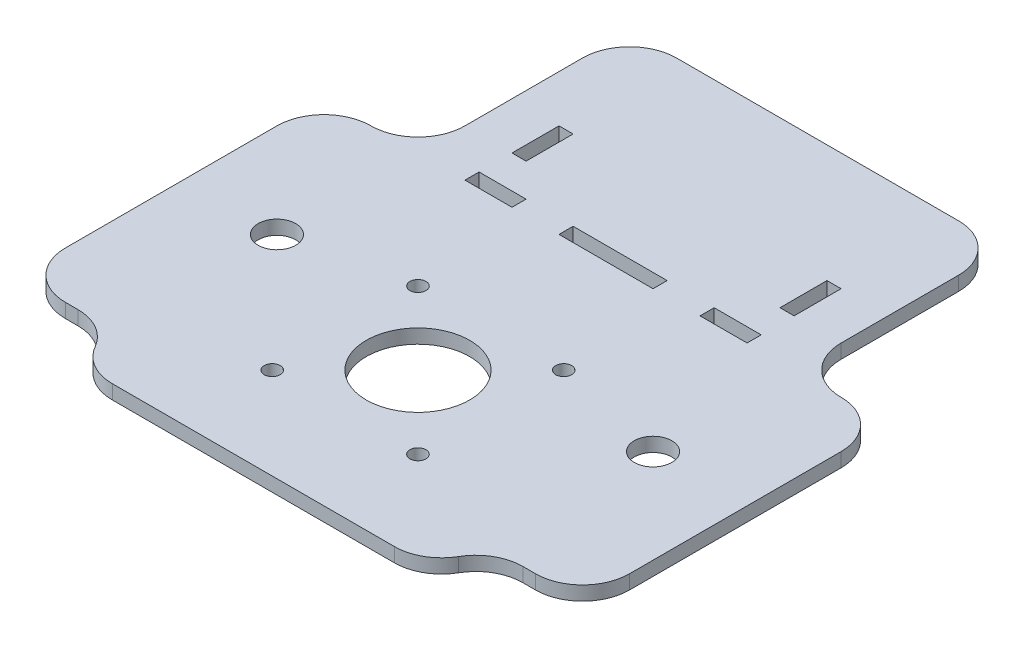
SolidWorks part; units mm, degrees
ref_plane "Front Plane" through (0, 0, 0) normal (0, 0, 1) x (1, 0, 0)
ref_plane "Top Plane" through (0, 0, 0) normal (0, 1, 0) x (1, 0, 0)
ref_plane "Right Plane" through (0, 0, 0) normal (1, 0, 0) x (0, 0, -1)
sketch "Sketch1" plane through (0, 0, 0) normal (0, 1, 0) x (1, 0, 0)
  line L1 (30, -45) -> (-30, -45)
  line L2 (30, -45) -> (30, 45)
  line L3 (30, 45) -> (-30, 45)
  line L4 (-30, -45) -> (-30, 45)
  line L5 (30, -45) -> (-30, 45) construction
  line L6 (30, 45) -> (-30, -45) construction
  point P0 (0, 0)
extrude "Boss-Extrude1" add sketch "Sketch1" along normal blind 3
sketch "Sketch2" plane through (0, 3, 0) normal (0, 1, 0) x (1, 0, 0)
  line L0 (30, 15) -> (20, 15)
  line L1 (30, 18) -> (20, 18)
  line L4 (-30, 45) -> (-30, -45)
  line L5 (-30, -45) -> (30, -45)
  line L6 (30, -45) -> (30, 45)
  line L7 (30, 45) -> (-30, 45)
  line L8 (-30, 35) -> (-30, 25)
  line L10 (30, 15) -> (30, 18)
  line L14 (-20, 18) -> (-20, 15)
  line L15 (-10, 18) -> (-10, 15)
  line L20 (-27, 35) -> (-27, 25)
  line L21 (-27, 25) -> (-30, 25)
  line L22 (27, 25) -> (27, 35)
  line L24 (10, 18) -> (10, 15)
  line L25 (20, 18) -> (20, 15)
  line L26 (10, 18) -> (-10, 18)
  line L27 (30, 18) -> (-30, 18) construction
  line L28 (10, 15) -> (-10, 15)
  line L29 (30, 15) -> (-30, 15) construction
  line L30 (-20, 18) -> (-30, 18)
  line L31 (-20, 15) -> (-30, 15)
  line L32 (30, 25) -> (27, 25)
  line L33 (-27, 35) -> (-30, 35)
  line L34 (30, 35) -> (27, 35)
  line L35 (-30, 18) -> (-30, 15)
  line L36 (30, 25) -> (30, 35)
  dimension "D1" = 0
  dimension "D3" = 3
extrude "Cut-Extrude2" cut sketch "Sketch2" against normal blind 3
sketch "Sketch3" plane through (0, 3, 0) normal (0, 1, 0) x (1, 0, 0)
  line L1 (40, -60) -> (-40, -60)
  line L2 (40, -60) -> (40, 60)
  line L3 (40, 60) -> (-40, 60)
  line L4 (-40, -60) -> (-40, 60)
  line L5 (40, -60) -> (-40, 60) construction
  line L6 (40, 60) -> (-40, -60) construction
  line L26 (-30, 18) -> (-20, 18)
  line L27 (-20, 18) -> (-20, 15)
  line L28 (-20, 15) -> (-30, 15)
  line L29 (-30, 15) -> (-30, -45)
  line L30 (-30, -45) -> (30, -45)
  line L31 (30, -45) -> (30, 15)
  line L32 (30, 15) -> (20, 15)
  line L33 (20, 15) -> (20, 18)
  line L34 (20, 18) -> (30, 18)
  line L35 (30, 18) -> (30, 25)
  line L36 (30, 25) -> (27, 25)
  line L37 (27, 25) -> (27, 35)
  line L38 (27, 35) -> (30, 35)
  line L39 (30, 35) -> (30, 45)
  line L40 (30, 45) -> (-30, 45)
  line L41 (-30, 45) -> (-30, 35)
  line L42 (-30, 35) -> (-27, 35)
  line L43 (-27, 35) -> (-27, 25)
  line L44 (-27, 25) -> (-30, 25)
  line L45 (-30, 25) -> (-30, 18)
  line L49 (-30, 18) -> (-30, -45)
  line L50 (-30, -45) -> (30, -45)
  line L51 (30, -45) -> (30, 18)
  line L55 (30, 18) -> (30, 25)
  line L59 (30, 25) -> (30, 45)
  line L60 (30, 45) -> (-30, 45)
  line L61 (-30, 45) -> (-30, 35)
  line L65 (-30, 35) -> (-30, 18)
  point P0 (0, 0)
  dimension "D1" = 0
extrude "Boss-Extrude2" add sketch "Sketch3" against normal blind 3
fillet "Fillet1" radius 10 2 edges at (-40, 1.5, 60) (40, 1.5, 60)
fillet "Fillet2" radius 10 2 edges at (-40, 1.5, -60) (40, 1.5, -60)
sketch "Sketch4" plane through (0, 3, 0) normal (0, 1, 0) x (1, 0, 0)
  circle A0 centre (15.5, -9.5) radius 1.7
  circle A1 centre (15.5, -40.5) radius 1.7
  circle A2 centre (-15.5, -40.5) radius 1.7
  circle A3 centre (-15.5, -9.5) radius 1.7
  point P1 (0, -25)
  point P9 (0, 15)
  point P14 (0, -25)
extrude "Cut-Extrude3" cut sketch "Sketch4" against normal blind 3
sketch "Sketch5" plane through (0, 3, 0) normal (0, 1, 0) x (1, 0, 0)
  circle A0 centre (0, -25) radius 11
extrude "Cut-Extrude4" cut sketch "Sketch5" against normal blind 3
sketch "Sketch6" plane through (0, 3, 0) normal (0, 1, 0) x (1, 0, 0)
  line L2 (60, -50) -> (60, 50)
  line L3 (60, -50) -> (60, 15)
  line L4 (60, -50) -> (40, -50)
  line L5 (-60, 50) -> (-60, -50)
  line L6 (-60, 15) -> (-60, -50)
  line L7 (60, 15) -> (40, 15)
  line L8 (-40, 50) -> (-40, -50) construction
  line L9 (40, -50) -> (40, 50) construction
  line L10 (-40, 15) -> (-40, -50)
  line L11 (40, -50) -> (40, 15)
  line L12 (-40, 15) -> (-60, 15)
  line L13 (60, 15) -> (-60, 15) construction
  line L14 (-40, -50) -> (-60, -50)
  line L15 (60, -50) -> (-60, -50) construction
  point P0 (-60, -50.195)
  dimension "D1" = 20
  dimension "D2" = 20
extrude "Boss-Extrude3" add sketch "Sketch6" against normal blind 3
fillet "Fillet3" radius 10 8 edges at (-40, 1.5, 50) (-60, 1.5, 50) (-40, 1.5, -15) (-60, 1.5, -15) (40, 1.5, -15) (60, 1.5, -15) (60, 1.5, 50) (40, 1.5, 50)
sketch "Sketch7" plane through (0, 3, 0) normal (0, 1, 0) x (1, 0, 0)
  circle A0 centre (-40, -15) radius 4
  circle A1 centre (40, -15) radius 4
extrude "Cut-Extrude5" cut sketch "Sketch7" against normal blind 3
